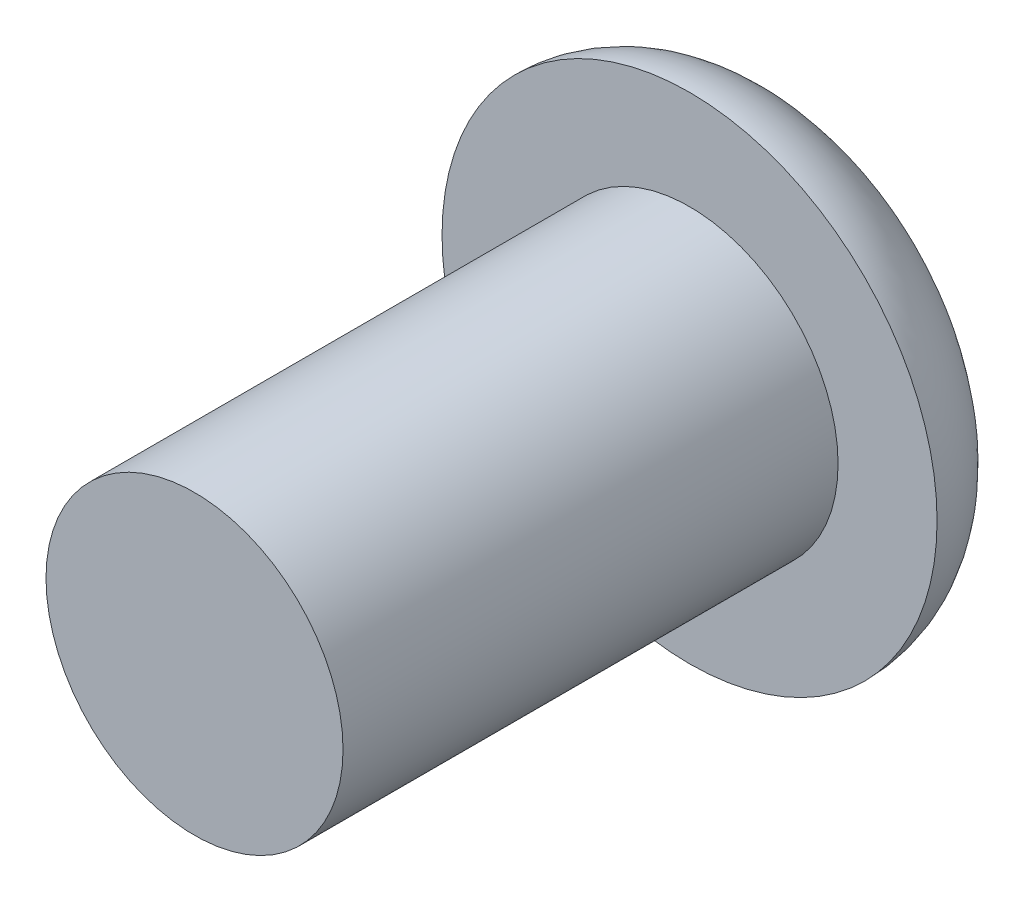
SolidWorks part; units mm, degrees
ref_plane "GAUCHE" through (0, 0, 0) normal (0, 0, 1) x (1, 0, 0)
ref_plane "Plan2" through (0, 0, 0) normal (0, 1, 0) x (1, 0, 0)
ref_plane "Plan3" through (0, 0, 0) normal (1, 0, 0) x (0, 0, -1)
sketch "Esquisse1" plane through (0, 0, 0) normal (0, 0, 1) x (1, 0, 0)
  circle A0 centre (0, 0) radius 5
  dimension "D1" = 10
extrude "Base-Extrusion" add sketch "Esquisse1" along normal blind 2
sketch "Esquisse2" plane through (0, 0, 2) normal (0, 0, 1) x (1, 0, 0)
  circle A0 centre (0, 0) radius 3
  dimension "D1" = 6
extrude "Boss.-Extru.1" add sketch "Esquisse2" along normal blind 10
fillet "Congé1" radius 2
sketch "Esquisse3" plane through (0, 0, 0) normal (0, 0, -1) x (-1, 0, 0)
  point P0 (0, 0)
sketch "Esquisse4" plane through (0, 0, 0) normal (0, 0, -1) x (-1, 0, 0)
  point P0 (0, 0)
